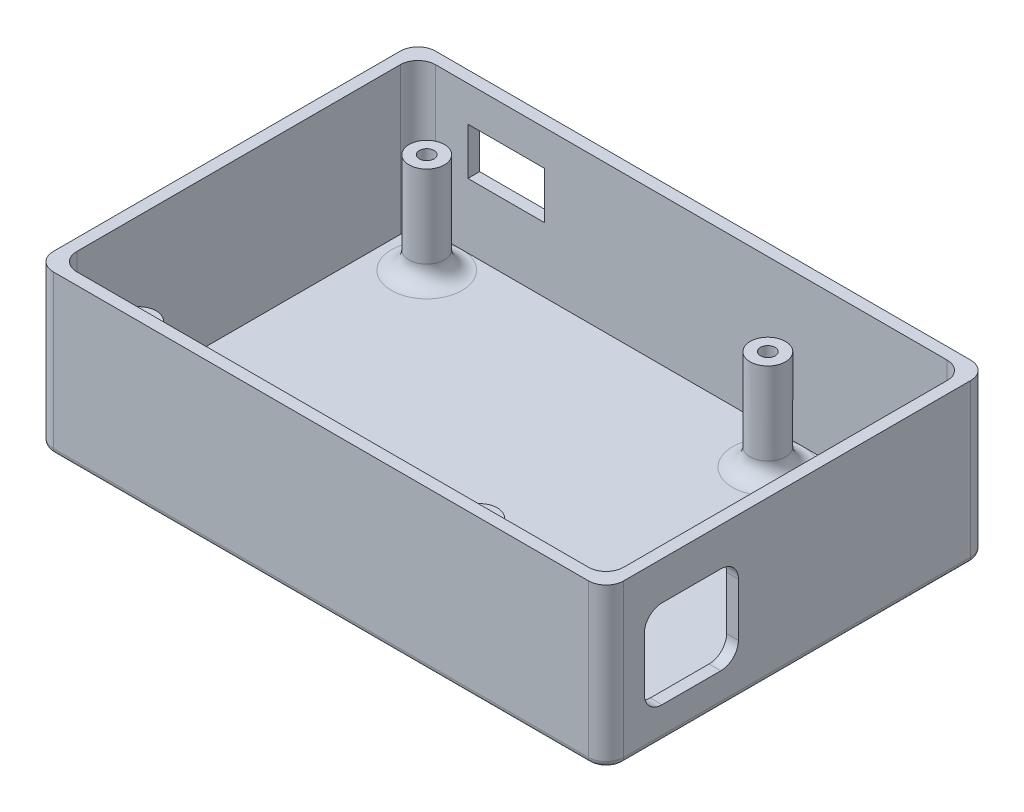
SolidWorks part; units mm, degrees
ref_plane "Front Plane" through (0, 0, 0) normal (0, 0, 1) x (1, 0, 0)
ref_plane "Top Plane" through (0, 0, 0) normal (0, 1, 0) x (1, 0, 0)
ref_plane "Right Plane" through (0, 0, 0) normal (1, 0, 0) x (0, 0, -1)
sketch "Sketch1" plane through (0, 0, 0) normal (0, 1, 0) x (1, 0, 0)
  line L1 (-48.5, 32.5) -> (48.5, 32.5)
  line L2 (-48.5, 32.5) -> (-48.5, -32.5)
  line L3 (-48.5, -32.5) -> (48.5, -32.5)
  line L4 (48.5, 32.5) -> (48.5, -32.5)
  line L5 (-48.5, 32.5) -> (48.5, -32.5) construction
  line L6 (-48.5, -32.5) -> (48.5, 32.5) construction
  point P0 (0, 0)
  dimension "D1" = 65
  dimension "D2" = 97
extrude "Boss-Extrude1" add sketch "Sketch1" along normal blind 2
sketch "Sketch3" plane through (0, 2, 0) normal (0, 1, 0) x (1, 0, 0)
  line L0 (46.5, 30.5) -> (-46.5, 30.5)
  line L1 (-46.5, 30.5) -> (-46.5, -30.5)
  line L2 (-46.5, -30.5) -> (46.5, -30.5)
  line L3 (46.5, -30.5) -> (46.5, 30.5)
  line L4 (48.5, -32.5) -> (48.5, 32.5)
  line L5 (48.5, 32.5) -> (-48.5, 32.5)
  line L6 (-48.5, 32.5) -> (-48.5, -32.5)
  line L7 (-48.5, -32.5) -> (48.5, -32.5)
  line L8 (48.5, -32.5) -> (48.5, 32.5)
  line L9 (48.5, 32.5) -> (-48.5, 32.5)
  line L10 (-48.5, 32.5) -> (-48.5, -32.5)
  line L11 (-48.5, -32.5) -> (48.5, -32.5)
  dimension "D1" = 0
  dimension "D2" = 2
extrude "Boss-Extrude2" add sketch "Sketch3" along normal blind 25
sketch "Sketch4" plane through (0, 2, 0) normal (0, 1, 0) x (1, 0, 0)
  line L0 (-46.5, 0) -> (46.5, 0) construction
  line L1 (-46.5, 30.5) -> (-46.5, -30.5) construction
  line L2 (46.5, -30.5) -> (46.5, 30.5) construction
  line L3 (-39, 27.7754) -> (-39, -22.5091) construction
  line L4 (-10, 25.9265) -> (-10, -25.8342) construction
  circle A0 centre (-39, 24.5) radius 3
  circle A1 centre (-39, -24.5) radius 3
  circle A2 centre (19, -24.5) radius 3
  circle A3 centre (19, 24.5) radius 3
  dimension "D1" = 6
  dimension "D2" = 49
  dimension "D3" = 58
  dimension "D4" = 27.5
extrude "Boss-Extrude3" add sketch "Sketch4" along normal blind 17
sketch "Sketch5" plane through (0, 19, 0) normal (0, 1, 0) x (1, 0, 0)
  circle A0 centre (-39, 24.5) radius 1.25
  circle A1 centre (19, 24.5) radius 1.25
  circle A2 centre (19, -24.5) radius 1.25
  circle A3 centre (-39, -24.5) radius 1.25
  dimension "D1" = 2.5
  dimension "D2" = 2.5
  dimension "D3" = 2.5
  dimension "D4" = 2.5
extrude "Cut-Extrude1" cut sketch "Sketch5" against normal blind 10
fillet "Fillet1" radius 3 4 edges at (-39, 2, 21.5) (19, 2, 27.5) (19, 2, -27.5) (-39, 2, -21.5)
fillet "Fillet2" radius 3 8 edges at (46.5, 14.5, -30.5) (48.5, 13.5, -32.5) (48.5, 13.5, 32.5) (46.5, 14.5, 30.5) (-46.5, 14.5, 30.5) (-48.5, 13.5, 32.5) (-48.5, 13.5, -32.5) (-46.5, 14.5, -30.5)
sketch "Sketch6" plane through (48.5, 0, 0) normal (1, 0, 0) x (0, 0, -1)
  line L0 (-18, 27) -> (-18, 0) construction
  line L1 (-29.5, 27) -> (29.5, 27) construction
  line L2 (-29.5, 0) -> (29.5, 0) construction
  line L3 (0, 0) -> (0, 27) construction
  line L4 (-26, 20.5) -> (-10, 20.5)
  line L5 (-26, 20.5) -> (-26, 5.5)
  line L6 (-26, 5.5) -> (-10, 5.5)
  line L7 (-10, 20.5) -> (-10, 5.5)
  line L8 (-26, 20.5) -> (-10, 5.5) construction
  line L9 (-26, 5.5) -> (-10, 20.5) construction
  point P6 (-18, 13)
  dimension "D1" = 16
  dimension "D2" = 15
  dimension "D3" = 18
  dimension "D4" = 13
extrude "Cut-Extrude2" cut sketch "Sketch6" against normal up to next
fillet "Fillet3" radius 3 4 edges at (47.5, 20.5, 26) (47.5, 20.5, 10) (47.5, 5.5, 10) (47.5, 5.5, 26)
sketch "Sketch7" plane through (0, 0, -32.5) normal (0, 0, -1) x (-1, 0, 0)
  line L0 (31.5, 27) -> (31.5, 0) construction
  line L1 (-45.5, 27) -> (45.5, 27) construction
  line L2 (-45.5, 0) -> (45.5, 0) construction
  line L3 (0, 0) -> (0, 27) construction
  line L4 (25, 21) -> (38, 21)
  line L5 (25, 21) -> (25, 13)
  line L6 (25, 13) -> (38, 13)
  line L7 (38, 21) -> (38, 13)
  line L8 (25, 21) -> (38, 13) construction
  line L9 (25, 13) -> (38, 21) construction
  point P6 (31.5, 17)
  dimension "D1" = 13
  dimension "D2" = 8
  dimension "D3" = 31.5
  dimension "D4" = 17
extrude "Cut-Extrude3" cut sketch "Sketch7" against normal up to next
fillet "Fillet4" radius 1 8 edges at (-47.6213, 0, -31.6213) (-48.5, 0, 0) (-47.6213, 0, 31.6213) (0, 0, 32.5) (47.6213, 0, 31.6213) (48.5, 0, 0) (47.6213, 0, -31.6213) (0, 0, -32.5)
